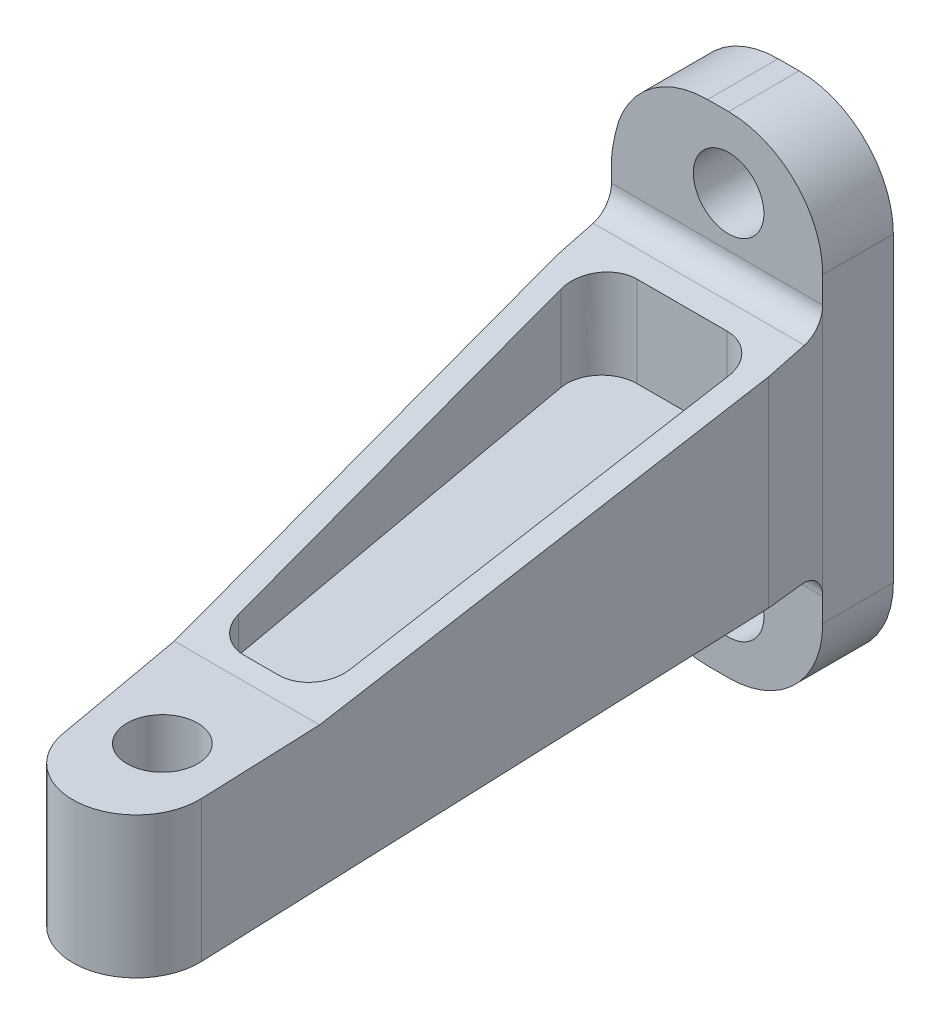
SolidWorks part; units mm, degrees
material "6061-T6 (SS)"
ref_plane "Front Plane" through (0, 0, 0) normal (0, 0, 1) x (1, 0, 0)
ref_plane "Top Plane" through (0, 0, 0) normal (0, 1, 0) x (1, 0, 0)
ref_plane "Right Plane" through (0, 0, 0) normal (1, 0, 0) x (0, 0, -1)
sketch "Sketch1" plane through (0, 0, 0) normal (0, 0, 1) x (1, 0, 0)
  line L8 (-28.5, -11.0464) -> (0, -11.0464)
  line L9 (-28.5, -17.3964) -> (-25.8774, -30.0964)
  line L10 (-25.8774, -30.0964) -> (0, -30.0964)
  line L11 (0, -30.0964) -> (0, 36.0645)
  line L12 (-28.5, 17.0145) -> (0, 17.0145)
  line L13 (-28.5, 23.3645) -> (-28.5, -17.3964)
  line L14 (-25.8774, 36.0645) -> (-28.5, 23.3645)
  line L15 (-25.8774, 36.0645) -> (0, 36.0645)
  circle A2 centre (-12.7, -20.5714) radius 4.7625
  circle A3 centre (-12.7, 26.5395) radius 4.7625
extrude "Boss-Extrude1" add sketch "Sketch1" along normal blind 9.525 contours L15 L14 L13 L12 L11 A3 | L8 L13 L9 L10 L11 A2 | L12 L13 L8 L11 region at (-14.25, 2.984, 0) region at (-14.25, -11.3892, 0) region at (-28.1572, 20.1895, 0)
sketch "Sketch2" plane through (0, 195.9337, -36.8296) normal (0, 0.9828, -0.1847) x (1, 0, 0)
  line L0 (71.608, 80.6018) -> (71.608, -49.3982) construction
  line L1 (71.608, 80.6018) -> (71.608, -49.3982)
  line L2 (71.608, 15.6018) -> (30.433, 15.6018)
  line L3 (30.433, -7.5988) -> (30.433, 15.6018)
  line L4 (30.433, 15.6018) -> (-5.144, -132.5874)
  dimension "D1" = 152.4
  dimension "D2" = 13.5
sketch "Sketch3" plane through (0, 0, 9.525) normal (0, 0, 1) x (1, 0, 0)
  line L0 (-28.5, -11.0464) -> (0, -11.0464) construction
  line L1 (-28.5, 17.0145) -> (0, 17.0145) construction
  line L2 (-28.5, -11.0464) -> (0, -11.0464)
  line L3 (-28.5, 17.0145) -> (0, 17.0145)
  line L4 (0, -30.0964) -> (0, 36.0645) construction
  line L5 (-28.5, 23.3645) -> (-28.5, -17.3964) construction
  line L6 (0, -11.0464) -> (0, 17.0145)
  line L7 (-28.5, 17.0145) -> (-28.5, -11.0464)
ref_plane "Plane1" through (0, -11.0464, 0) normal (0, 1, 0) x (1, 0, 0)
sketch "Sketch4" plane through (0, -11.0464, 0) normal (0, 1, 0) x (1, 0, 0)
  line L4 (-14.25, -9.525) -> (-5.144, -93.4757)
  line L5 (-5.144, -93.4757) -> (-3.7745, -106.1017)
  dimension "D1" = 12.7
sweep "Sweep1" add profiles "Sketch3" path "Sketch4"
sketch "Sketch5" plane through (0, 17.0145, 0) normal (0, 1, 0) x (1, 0, 0)
  line L0 (9.106, -93.4757) -> (-19.394, -93.4757) construction
  line L1 (-0.3815, -93.4757) -> (-19.394, -93.4757) construction
  circle A0 centre (-5.144, -93.4757) radius 4.7625
chamfer "Chamfer1" distance 88.9 angle 4 1 edges at (10.4755, 2.984, 106.1017) first distance on face at (9.7907, 2.984, 99.7887)
chamfer "Chamfer2" distance 88.9 angle 4 1 edges at (-18.0245, 2.984, 106.1017) first distance on face at (-18.7093, 2.984, 99.7887)
fillet "Fillet1" 2 edges at (-11.7238, 2.984, 106.1017) (4.2696, 2.984, 106.1017) type full round first side face at (-17.7761, 2.984, 72.4325) second side face at (2.9817, 2.984, 72.4325) middle face at (-3.7271, 2.984, 106.1017)
sketch "Sketch6" plane through (-28.5, 0, 0) normal (-1, 0, 0) x (0, 0, 1)
  line L0 (93.4757, -11.0464) -> (17.7201, -11.0464) construction
  line L1 (93.4757, -11.0464) -> (17.7201, -11.0464)
  line L3 (106.1017, 8.0036) -> (80.7017, 8.0036)
  line L6 (0, 23.3645) -> (0, -17.3964)
  line L7 (0, -17.3964) -> (9.525, -17.3964)
  line L8 (9.525, -17.3964) -> (9.525, -11.0464)
  line L9 (9.525, -11.0464) -> (9.525, 17.0145)
  line L11 (9.525, 23.3645) -> (0, 23.3645)
  line L12 (0, 23.3645) -> (0, -17.3964)
  line L13 (0, -17.3964) -> (9.525, -17.3964)
  line L14 (9.525, -17.3964) -> (9.525, -11.0464)
  line L15 (9.525, -11.0464) -> (9.525, 17.0145)
  line L17 (9.525, 23.3645) -> (0, 23.3645)
  line L20 (80.7017, -11.0464) -> (106.1017, -11.0464)
  line L21 (106.1017, -11.0464) -> (106.1017, 17.0145) construction
  line L22 (106.1017, -11.0464) -> (106.1017, 8.0036)
  line L25 (9.525, 17.0145) -> (17.7201, 36.9013)
  line L26 (17.7201, 36.9013) -> (128.3277, 30.3781)
  line L27 (128.3277, 30.3781) -> (114.7061, -29.4575)
  line L28 (114.7061, -29.4575) -> (80.7017, -11.0464)
  line L29 (80.7017, 8.0036) -> (9.525, 17.0145)
  line L35 (9.525, 17.0145) -> (9.525, 23.3645)
  line L36 (9.525, 17.0145) -> (9.525, 23.3645)
  dimension "D2" = 0
  dimension "D3" = 25.4
  dimension "D4" = 19.05
  dimension "D5" = 25.4
  dimension "D1" = 0
extrude "Cut-Extrude2" cut sketch "Sketch6" against normal through all contours L28 L27 L26 L25 L22 L20 region at (-28.5, 15.795, 78.1541)
fillet "Fillet4" radius 3.175 2 edges at (-14.25, -11.0464, 9.525) (-14.25, 17.0145, 9.525)
sketch "Sketch9" plane through (-28.5, 0, 0) normal (-1, 0, 0) x (0, 0, 1)
  line L0 (80.7017, -11.0464) -> (80.7017, 8.0036)
  line L1 (99.0819, -11.0464) -> (17.7201, -11.0464) construction
  line L2 (80.7017, -1.5214) -> (17.7201, 2.4653)
  line L3 (17.7201, -11.0464) -> (17.7201, 15.977) construction
ref_plane "Plane3" through (0, 2.4653, 0) normal (0, 1, 0) x (1, 0, 0)
fillet "Fillet5" radius 12.7 1 edges at (-28.5, 23.3645, 4.7625)
fillet "Fillet6" radius 12.7 2 edges at (0, 36.0645, 4.7625) (-25.8774, 36.0645, 4.7625)
sketch "Sketch15" plane through (0, 8.0036, 0) normal (0, 1, 0) x (1, 0, 0)
  circle A0 centre (-5.144, -93.4757) radius 4.7625
extrude "Cut-Extrude7" cut sketch "Sketch15" against normal through all
fillet "Fillet9" radius 12.7 3 edges at (-28.5, -17.3964, 4.7625) (0, -30.0964, 4.7625) (-25.8774, -30.0964, 4.7625)
ref_plane "Plane4" through (0, 19.8129, 0) normal (0, 1, 0) x (1, 0, 0)
sketch "Sketch17" plane through (0, 19.8129, 0) normal (0, 1, 0) x (1, 0, 0)
  line L2 (-24.6636, -15.4669) -> (-24.4661, -17.2874)
  line L3 (-2.2796, -17.9615) -> (-2.5503, -15.4669)
  line L8 (-6.9603, -15.4669) -> (-19.1063, -15.4669)
  line L9 (-0.1706, -73.0921) -> (-2.2012, -20.0125)
  line L10 (-9.5639, -77.9961) -> (-4.9297, -77.9961)
  line L11 (-23.7948, -21.0212) -> (-14.2524, -74.1009)
  ellipse E8 centre (-19.1063, -20.1917) end of major axis (-14.3438, -20.1917) minor radius 4.7248 (-19.1063, -15.4669) -> (-23.7948, -21.0212) ccw
  ellipse E9 centre (-6.9603, -20.1917) end of major axis (-2.1978, -20.1917) minor radius 4.7248 (-2.2012, -20.0125) -> (-6.9603, -15.4669) ccw
  ellipse E10 centre (-4.9297, -73.2713) end of major axis (-9.6922, -73.2713) minor radius 4.7248 (-4.9297, -77.9961) -> (-0.1706, -73.0921) ccw
  ellipse E11 centre (-9.5639, -73.2713) end of major axis (-14.3264, -73.2713) minor radius 4.7248 (-14.2524, -74.1009) -> (-9.5639, -77.9961) ccw
  dimension "D1" = 62.5292
sketch "Sketch18" plane through (0, -11.0464, 0) normal (0, -1, 0) x (1, 0, 0)
  line L0 (-2.2796, 17.9615) -> (-2.5503, 15.4669) construction
  line L1 (-24.6636, 15.4669) -> (-24.4661, 17.2874) construction
  line L2 (-2.2796, 17.9615) -> (-2.5503, 15.4669)
  line L3 (-24.6636, 15.4669) -> (-24.4661, 17.2874)
  line L4 (-4.9297, 77.9961) -> (-9.5639, 77.9961)
  line L5 (-14.2524, 74.1009) -> (-23.7948, 21.0212)
  line L6 (-19.1063, 15.4669) -> (-6.9603, 15.4669)
  line L7 (-2.2012, 20.0125) -> (-0.1706, 73.0921)
  line L8 (-4.9297, 77.9961) -> (-9.5639, 77.9961)
  line L9 (-14.2524, 74.1009) -> (-23.7948, 21.0212)
  line L10 (-19.1063, 15.4669) -> (-6.9603, 15.4669)
  line L11 (-2.2012, 20.0125) -> (-0.1706, 73.0921)
  ellipse E4 centre (-4.9297, 73.2713) end of major axis (-9.6922, 73.2713) minor radius 4.7248 (-0.1706, 73.0921) -> (-4.9297, 77.9961) ccw
  ellipse E5 centre (-9.5639, 73.2713) end of major axis (-14.3264, 73.2713) minor radius 4.7248 (-9.5639, 77.9961) -> (-14.2524, 74.1009) ccw
  ellipse E6 centre (-19.1063, 20.1917) end of major axis (-14.3438, 20.1917) minor radius 4.7248 (-23.7948, 21.0212) -> (-19.1063, 15.4669) ccw
  ellipse E7 centre (-6.9603, 20.1917) end of major axis (-2.1978, 20.1917) minor radius 4.7248 (-6.9603, 15.4669) -> (-2.2012, 20.0125) ccw
  ellipse E8 centre (-4.9297, 73.2713) end of major axis (-9.6922, 73.2713) minor radius 4.7248 (-0.1706, 73.0921) -> (-4.9297, 77.9961) ccw
  ellipse E9 centre (-9.5639, 73.2713) end of major axis (-14.3264, 73.2713) minor radius 4.7248 (-9.5639, 77.9961) -> (-14.2524, 74.1009) ccw
  ellipse E10 centre (-19.1063, 20.1917) end of major axis (-14.3438, 20.1917) minor radius 4.7248 (-23.7948, 21.0212) -> (-19.1063, 15.4669) ccw
  ellipse E11 centre (-6.9603, 20.1917) end of major axis (-2.1978, 20.1917) minor radius 4.7248 (-6.9603, 15.4669) -> (-2.2012, 20.0125) ccw
  dimension "D1" = 0
extrude "Cut-Extrude8" cut sketch "Sketch17" against normal offset from surface (15.7601 mm away) 1.5875 contours L11 E11 L10 E10 L9 E9 L8 E8 region at (-10.4378, 19.8129, 44.2082) up to plane "Plane3"
extrude "Cut-Extrude9" cut sketch "Sketch18" against normal offset from surface (11.9242 mm away) 1.5875 contours L10 E11 L11 E8 L8 E9 L9 E10 region at (-10.4378, -11.0464, 44.2082) up to plane "Plane3"
move or copy body "Body-Move/Copy2" [suppressed] bodies to move or copy 114
move or copy body "Body-Move/Copy1" [suppressed] bodies to move or copy 114
